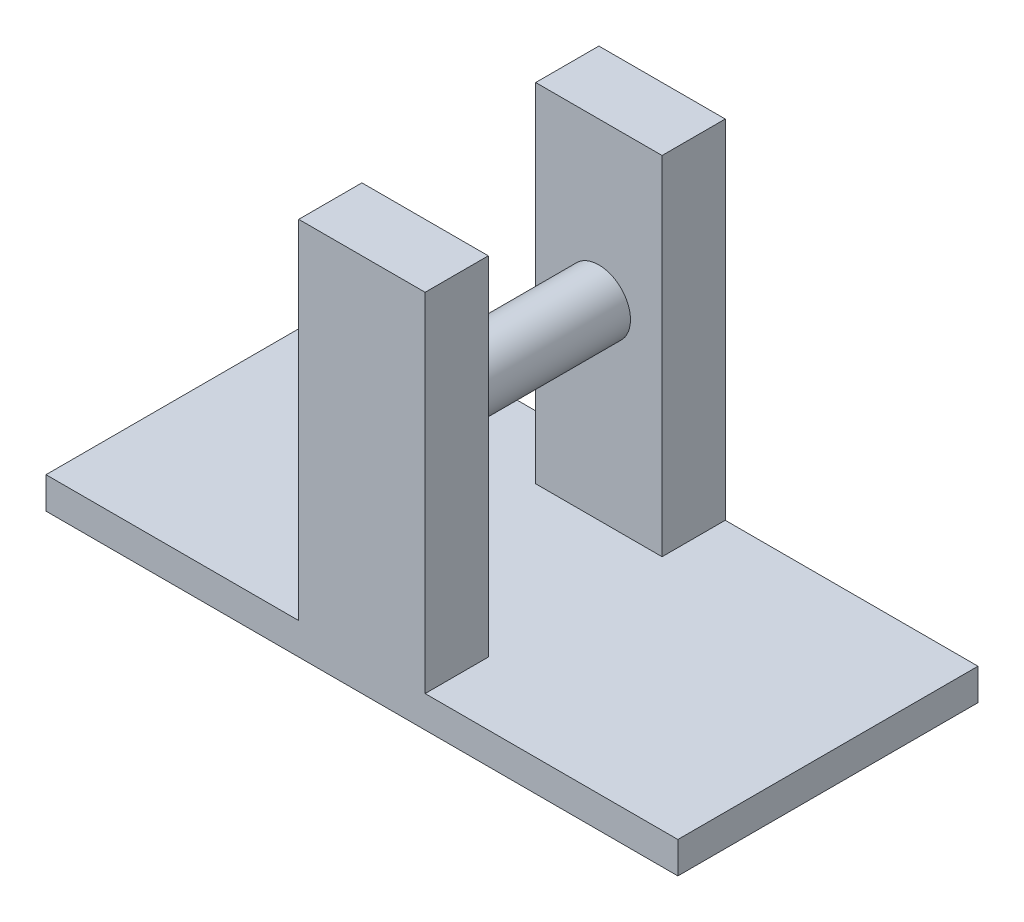
SolidWorks part; units mm, degrees
ref_plane "Front Plane" through (0, 0, 0) normal (0, 0, 1) x (1, 0, 0)
ref_plane "Top Plane" through (0, 0, 0) normal (0, 1, 0) x (1, 0, 0)
ref_plane "Right Plane" through (0, 0, 0) normal (1, 0, 0) x (0, 0, -1)
sketch "Sketch2" plane through (0, 0, 0) normal (0, 1, 0) x (1, 0, 0)
  line L1 (-127, -60.325) -> (127, -60.325)
  line L2 (-127, -60.325) -> (-127, 60.325)
  line L3 (-127, 60.325) -> (127, 60.325)
  line L4 (127, -60.325) -> (127, 60.325)
  line L5 (-127, -60.325) -> (127, 60.325) construction
  line L6 (-127, 60.325) -> (127, -60.325) construction
  point P0 (0, 0)
  dimension "D1" = 120.65
  dimension "D2" = 254
extrude "Boss-Extrude2" add sketch "Sketch2" along normal blind 12.7
sketch "Sketch4" plane through (0, 12.7, 0) normal (0, 1, 0) x (1, 0, 0)
  line L0 (-127, -60.325) -> (0, -60.325) construction
  line L1 (-127, -60.325) -> (127, -60.325) construction
  line L2 (0, -60.325) -> (0, -47.625) construction
  line L3 (0, -47.625) -> (25.4, -47.625) construction
  line L4 (25.4, -47.625) -> (25.4, -34.925) construction
  line L6 (-25.4, -60.325) -> (25.4, -60.325)
  line L7 (-25.4, -60.325) -> (-25.4, -34.925)
  line L8 (-25.4, -34.925) -> (25.4, -34.925)
  line L9 (25.4, -60.325) -> (25.4, -34.925)
  line L10 (-25.4, -60.325) -> (25.4, -34.925) construction
  line L11 (-25.4, -34.925) -> (25.4, -60.325) construction
  dimension "D1" = 12.7
  dimension "D2" = 25.4
  dimension "D3" = 12.7
extrude "Boss-Extrude3" add sketch "Sketch4" along normal blind 139.7
mirror "Mirror1" about plane through (0, 0, 0) normal (0, 0, 1) of "Boss-Extrude3"
sketch "Sketch11" plane through (0, 0, 60.325) normal (0, 0, 1) x (1, 0, 0)
  line L0 (0, 0) -> (0, 88.9) construction
  line L2 (-127, 0) -> (127, 0) construction
  circle A1 centre (0, 88.9) radius 12.7
  dimension "D2" = 25.4
  dimension "D1" = 88.9
extrude "Boss-Extrude4" add sketch "Sketch11" against normal up to surface (95.25 mm away) up to face at (0, 82.55, -34.925)
